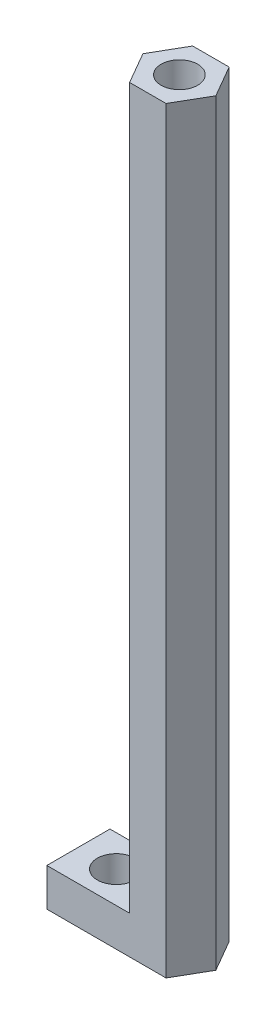
SolidWorks part; units mm, degrees
ref_plane "Front Plane" through (0, 0, 0) normal (0, 0, 1) x (1, 0, 0)
ref_plane "Top Plane" through (0, 0, 0) normal (0, 1, 0) x (1, 0, 0)
ref_plane "Right Plane" through (0, 0, 0) normal (1, 0, 0) x (0, 0, -1)
sketch "Sketch2" plane through (0, 0, 0) normal (0, 1, 0) x (1, 0, 0)
  line L0 (8, 2.5) -> (-3, 2.5)
  line L1 (-3, 2.5) -> (-3, -2.5)
  line L2 (-3, -2.5) -> (8, -2.5)
  line L3 (8, -2.5) -> (8, 2.5)
  line L6 (3.5566, 2.5) -> (2.1132, 0)
  line L7 (2.1132, 0) -> (3.5566, -2.5)
  line L8 (3.5566, -2.5) -> (6.4434, -2.5)
  line L9 (6.4434, -2.5) -> (7.8868, 0)
  line L10 (7.8868, 0) -> (6.4434, 2.5)
  line L11 (6.4434, 2.5) -> (3.5566, 2.5)
  circle A0 centre (0, 0) radius 1.5
  circle A1 centre (5, 0) radius 2.5 construction
  point P5 (0, 0)
  point P9 (6.1924, -1.6878)
  dimension "D1" = 3
  dimension "D2" = 5
  dimension "D3" = 2.5
  dimension "D4" = 3
  dimension "D5" = 8
  dimension "D6" = 5
extrude "Boss-Extrude1" add sketch "Sketch2" along normal blind 3 contours L7 L6 L0 L1 L2 A0 | L10 L9 L2 L3 L0 | L9 L10 L0 L6 L7 L2 region at (7.9476, 0, 0) region at (5, 0, 0) region at (2.7635, 0, -1.2912)
extrude "Boss-Extrude2" add sketch "Sketch2<3>" along normal blind 60 contours L9 L10 L11 L6 L7 L8
sketch "Sketch2<3>" plane through (0, 0, 0) normal (0, 1, 0) x (1, 0, 0) same geometry as "Sketch2"
sketch "Sketch3" plane through (0, 60, 0) normal (0, 1, 0) x (1, 0, 0)
  line L0 (6.4434, 2.5) -> (3.5566, 2.5) construction
  circle A0 centre (5, 0) radius 1.45
  dimension "D1" = 2.9
  dimension "D2" = 5
  dimension "D3" = 2.5
extrude "Cut-Extrude1" cut sketch "Sketch3" against normal blind 10
sketch "Sketch4" plane through (0, 3, 0) normal (0, 1, 0) x (1, 0, 0)
  line L0 (6.4434, 2.5) -> (8, 2.5)
  line L1 (8, 2.5) -> (8, -2.5)
  line L2 (8, -2.5) -> (6.4434, -2.5)
  line L3 (6.4434, -2.5) -> (7.8868, 0)
  line L4 (7.8868, 0) -> (6.4434, 2.5)
extrude "Cut-Extrude2" cut sketch "Sketch4" against normal blind 8
sketch "Sketch5" plane through (0, 3, 0) normal (0, 1, 0) x (1, 0, 0)
  line L0 (3.5566, 2.5) -> (-3, 2.5) construction
  circle A0 centre (0, 0) radius 2.5
extrude "Cut-Extrude3" cut sketch "Sketch5" along normal blind 3
chamfer "Chamfer1" distance 1 angle 45 2 edges at (2.2749, 6, 0.2799) (2.2749, 6, -0.2799)
